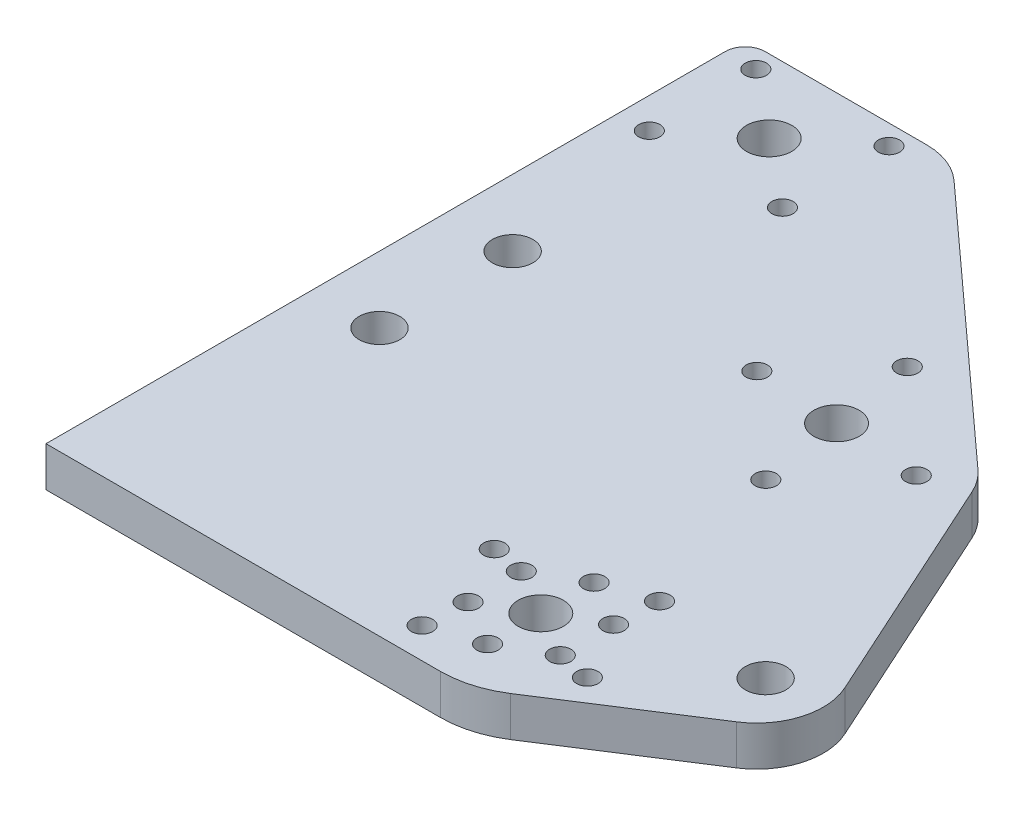
SolidWorks part; units mm, degrees
material "Policarbonato"
ref_plane "Plano frontal" through (0, 0, 0) normal (0, 0, 1) x (1, 0, 0)
ref_plane "Plano superior" through (0, 0, 0) normal (0, 1, 0) x (1, 0, 0)
ref_plane "Plano direito" through (0, 0, 0) normal (1, 0, 0) x (0, 0, -1)
ref_plane "Plano1" through (0, -6, 0) normal (0, -1, 0) x (1, 0, 0)
sketch "Esboço1" plane through (0, -6, 0) normal (0, -1, 0) x (1, 0, 0)
  line L0 (151.2357, -14.2909) -> (167.1948, 20.7865)
  line L1 (163.5005, 33.3393) -> (142.8288, 46.6294)
  line L2 (134.6661, 49.0269) -> (75.4374, 49.0269)
  line L3 (75.4374, 49.0269) -> (75.4374, -53)
  line L4 (78.4374, -56) -> (102.6847, -56)
  line L5 (109.4101, -53.4005) -> (148.859, -17.5502)
  line L6 (134.1775, -0.3541) -> (144.9383, -12.195) construction
  line L7 (144.9383, -12.195) -> (130.1372, -25.6459) construction
  line L8 (130.1372, -25.6459) -> (119.3765, -13.805) construction
  line L9 (119.3765, -13.805) -> (134.1775, -0.3541) construction
  line L10 (134.1775, -0.3541) -> (130.1372, -25.6459) construction
  line L11 (100.0374, -37) -> (80.0374, -53) construction
  line L12 (127.326, 44.4269) -> (146.5154, 38.7906) construction
  line L13 (146.5154, 38.7906) -> (142.0063, 23.4391) construction
  line L14 (142.0063, 23.4391) -> (122.8169, 29.0754) construction
  line L15 (122.8169, 29.0754) -> (127.326, 44.4269) construction
  line L16 (127.326, 44.4269) -> (142.0063, 23.4391) construction
  line L17 (134.6661, 33.933) -> (138.9199, 48.4151) construction
  circle A0 centre (119.3765, -13.805) radius 1.6
  circle A1 centre (146.5154, 38.7906) radius 1.6
  circle A2 centre (142.0063, 23.4391) radius 1.6
  circle A3 centre (159.9953, 25.4877) radius 3.05
  circle A4 centre (100.0374, -37) radius 1.6
  circle A5 centre (100.0374, -53) radius 1.6
  circle A6 centre (80.0374, -37) radius 1.6
  circle A7 centre (80.0374, -53) radius 1.6
  circle A8 centre (122.8169, 29.0754) radius 1.6
  circle A9 centre (127.326, 44.4269) radius 1.6
  circle A10 centre (130.1372, -25.6459) radius 1.6
  circle A11 centre (144.9383, -12.195) radius 1.6
  circle A12 centre (134.1775, -0.3541) radius 1.6
  circle A13 centre (141.5943, 29.933) radius 1.6
  circle A14 centre (134.6661, 25.933) radius 1.6
  circle A15 centre (127.7379, 29.933) radius 1.6
  circle A16 centre (127.7379, 37.933) radius 1.6
  circle A17 centre (134.6661, 41.933) radius 1.6
  circle A18 centre (141.5943, 37.933) radius 1.6
  circle A19 centre (134.6661, 33.933) radius 3.4
  circle A20 centre (132.1574, -13) radius 3.4
  circle A21 centre (90.0374, -45) radius 3.4
  arc A22 (167.1948, 20.7865) -> (163.5005, 33.3393) centre (158.0926, 24.9277) ccw
  arc A23 (142.8288, 46.6294) -> (134.6661, 49.0269) centre (134.6661, 33.933) ccw
  arc A24 (75.4374, -53) -> (78.4374, -56) centre (78.4374, -53) ccw
  arc A25 (102.6847, -56) -> (109.4101, -53.4005) centre (102.6847, -46) ccw
  arc A26 (148.859, -17.5502) -> (151.2357, -14.2909) centre (142.1335, -10.1497) ccw
  point P62 (134.6661, 33.933)
  dimension "D4" = 10
  dimension "D5" = 6.1
  dimension "D8" = 6.8
  dimension "D9" = 3.2
  dimension "D24" = 3
  dimension "D1" = 105.0269
  dimension "D2" = 11
  dimension "D3" = 82.6552
  dimension "D6" = 80.9277
  dimension "D7" = 137.736
  dimension "D10" = 20
  dimension "D11" = 16
  dimension "D12" = 6.6
  dimension "D13" = 52.897
  dimension "D14" = 43
  dimension "D15" = 16
  dimension "D16" = 90.676
  dimension "D17" = 59.2287
  dimension "D18" = 14.6
  dimension "D19" = 8
  dimension "D21" = 26.7
  dimension "D22" = 47.5
  dimension "D23" = 6.6
  dimension "D20" = 6
extrude "Ressalto-extrusão1" add sketch "Esboço1" against normal blind 6
sketch "Esboço2" plane through (0, -6, 0) normal (0, -1, 0) x (1, 0, 0)
  line L0 (75.4374, 49.0269) -> (75.4374, -53) construction
  line L1 (78.428, 16.433) -> (146.9239, 16.433) construction
  circle A0 centre (85.4374, 8.933) radius 3.05
  circle A1 centre (85.4374, -11.067) radius 3.05
  circle A2 centre (85.4374, 8.933) radius 7.5 construction
  circle A3 centre (85.4374, -11.067) radius 7.5 construction
  circle A4 centre (134.6661, 33.933) radius 3.4 construction
  dimension "D1" = 6.1
  dimension "D2" = 15
  dimension "D3" = 20
  dimension "D5" = 25
  dimension "D4" = 10
extrude "Corte-extrusão1" cut sketch "Esboço2" against normal blind 10 contours A1 | A0 region at (85.4374, -6, -11.067)
sketch "Esboço3" plane through (0, -6, 0) normal (0, -1, 0) x (1, 0, 0)
  line L0 (84.7148, -42.8247) -> (118.7445, 40.4401) construction
  line L1 (94.6454, -48.4394) -> (148.4498, 23.6447) construction
  line L2 (84.0455, -40.4974) -> (115.1755, 35.6722) construction
  circle A0 centre (134.6661, 33.933) radius 17.2 construction
  circle A1 centre (90.0374, -45) radius 5.75 construction
  circle A2 centre (85.4374, -11.067) radius 7.5 construction
  circle A3 centre (132.1574, -13) radius 10.75 construction
  dimension "D1" = 34.4
  dimension "D2" = 11.5
  dimension "D3" = 15
  dimension "D4" = 21.5
  dimension "D5" = 1.5
